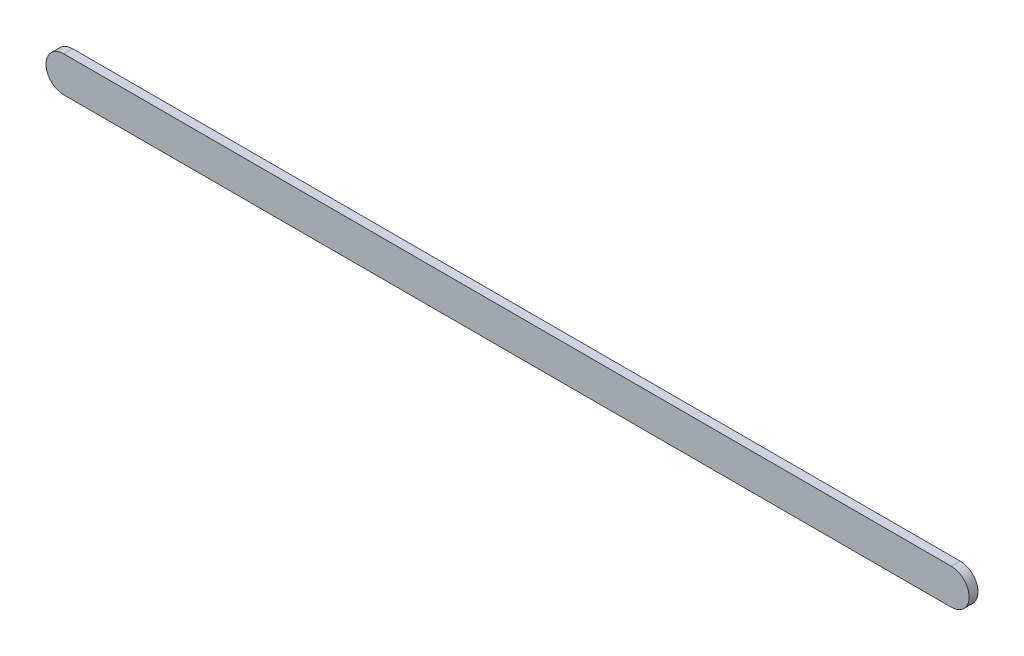
SolidWorks part; units mm, degrees
ref_plane "Front Plane" through (0, 0, 0) normal (0, 0, 1) x (1, 0, 0)
ref_plane "Top Plane" through (0, 0, 0) normal (0, 1, 0) x (1, 0, 0)
ref_plane "Right Plane" through (0, 0, 0) normal (1, 0, 0) x (0, 0, -1)
sketch "Sketch2" plane through (0, 0, 0) normal (0, 0, 1) x (1, 0, 0)
  line L0 (-75.9378, 0) -> (174.0622, 0) construction
  line L1 (-75.9378, 5) -> (174.0622, 5)
  line L2 (-75.9378, -5) -> (174.0622, -5)
  arc A0 (-75.9378, 5) -> (-75.9378, -5) centre (-75.9378, 0) ccw
  arc A1 (174.0622, -5) -> (174.0622, 5) centre (174.0622, 0) ccw
  point P3 (49.0622, 0)
  dimension "D1" = 5
  dimension "D2" = 250
extrude "Boss-Extrude1" add sketch "Sketch2" along normal blind 2.5
sketch "Sketch3" plane through (0, 0, 2.5) normal (0, 0, 1) x (1, 0, 0)
  point P0 (-75.9378, 0)
  point P1 (174.0622, 0)
ref_axis "Axis2" through (-75.9378, 0, 2.5) along (0, 0, 1)
ref_axis "Axis3" through (174.0622, 0, 2.5) along (0, 0, 1)
